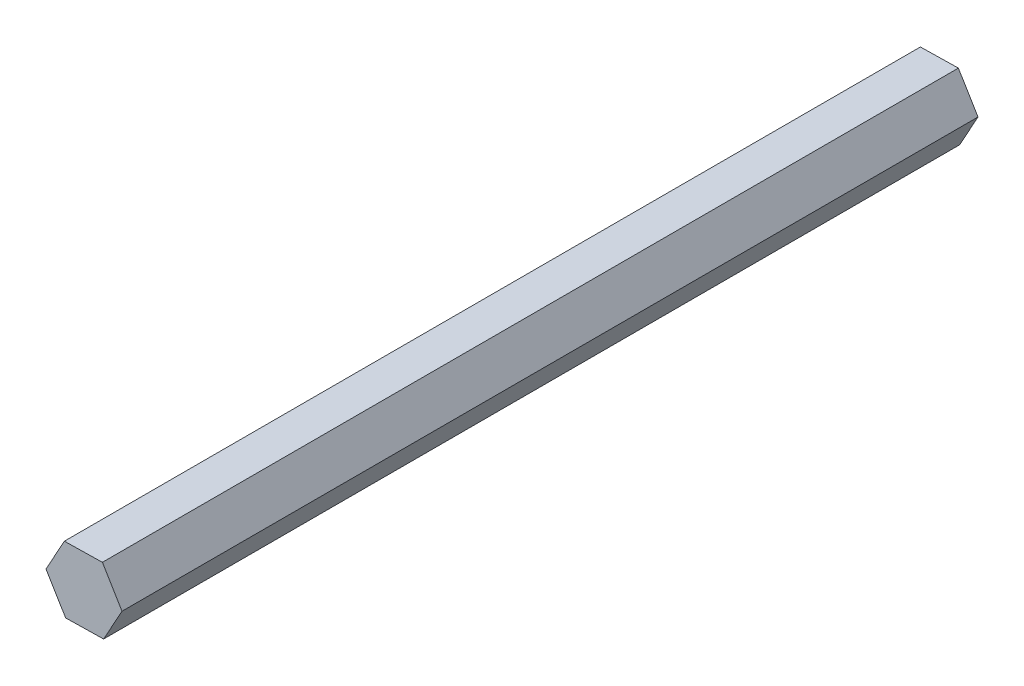
SolidWorks part; units mm, degrees
ref_plane "Front Plane" through (0, 0, 0) normal (0, 0, 1) x (1, 0, 0)
ref_plane "Top Plane" through (0, 0, 0) normal (0, 1, 0) x (1, 0, 0)
ref_plane "Right Plane" through (0, 0, 0) normal (1, 0, 0) x (0, 0, -1)
sketch "Sketch1" plane through (0, 0, 0) normal (0, 0, 1) x (1, 0, 0)
  line L1 (3.7846, -6.2802) -> (7.3311, 0.1374)
  line L2 (7.3311, 0.1374) -> (3.5465, 6.4176)
  line L3 (3.5465, 6.4176) -> (-3.7846, 6.2802)
  line L4 (-3.7846, 6.2802) -> (-7.3311, -0.1374)
  line L5 (-7.3311, -0.1374) -> (-3.5465, -6.4176)
  line L6 (-3.5465, -6.4176) -> (3.7846, -6.2802)
  circle A0 centre (0, 0) radius 6.35 construction
  dimension "D1" = 12.7
extrude "Boss-Extrude1" add sketch "Sketch1" along normal blind 165.1
